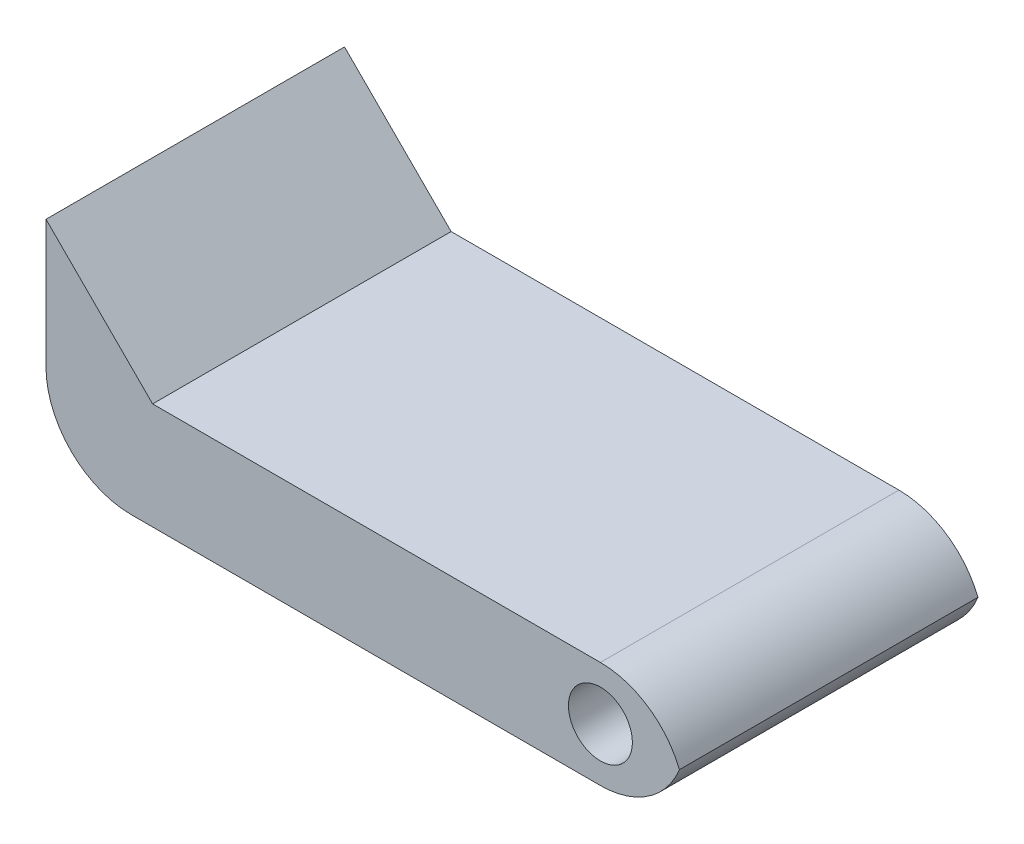
SolidWorks part; units mm, degrees
ref_plane "Front Plane" through (0, 0, 0) normal (1, 0, 0) x (0, 1, 0)
ref_plane "Top Plane" through (0, 0, 0) normal (0, 0, 1) x (0, 1, 0)
ref_plane "Right Plane" through (0, 0, 0) normal (0, 1, 0) x (-1, 0, 0)
sketch "Sketch1" plane through (0, 0, 0) normal (0, 0, 1) x (0, 1, 0)
  line L0 (0, 0) -> (0, 31.75)
  line L1 (0, -55) -> (0, 55) construction
  line L2 (0, 31.75) -> (6.35, 38.1)
  line L3 (6.35, 38.1) -> (-6.35, 38.1)
  line L4 (-6.35, 38.1) -> (-6.35, 0)
  line L5 (-55, 0) -> (55, 0) construction
  line L6 (-6.35, 0) -> (0, 0)
  dimension "D1" = 31.75
  dimension "D2" = 38.1
  dimension "D3" = 12.7
  dimension "D4" = 6.35
extrude "Boss-Extrude1" add sketch "Sketch1" along normal blind 17.78
sketch "Sketch3" plane through (0, 0, 17.78) normal (0, 0, 1) x (1, 0, 0)
  line L5 (0, -55) -> (0, 55) construction
  line L6 (-38.1, -6.35) -> (0, -6.35) construction
  circle A3 centre (-5.08, -3.175) radius 1.905
  point P4 (0, 0)
  point P5 (0, 0)
  point P6 (0, 0)
  dimension "D1" = 3.81
  dimension "D2" = 5.08
  dimension "D3" = 3.175
fillet "Fillet2" radius 5.08 3 edges at (-38.1, -6.35, 8.89) (0, 0, 8.89) (0, -6.35, 8.89)
extrude "Cut-Extrude1" cut sketch "Sketch3" against normal through all
